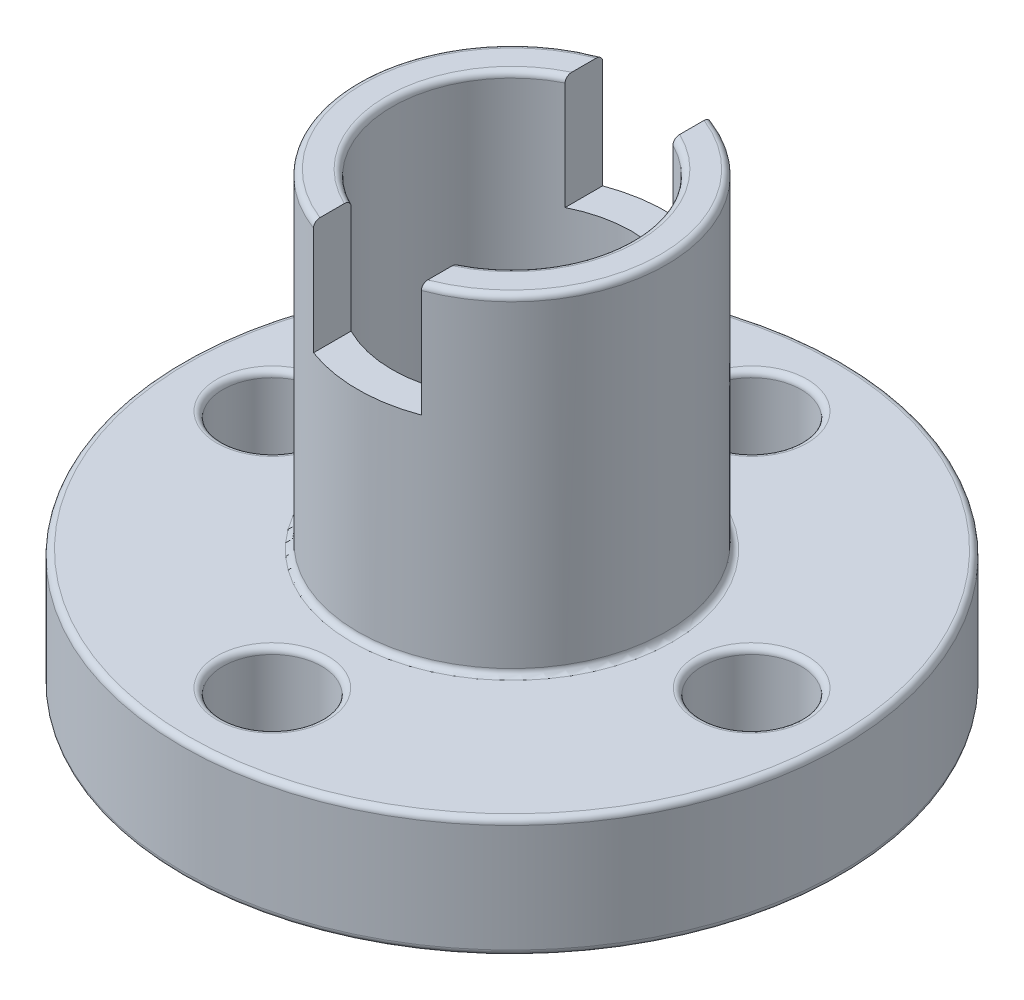
SolidWorks part; units mm, degrees
ref_plane "前视基准面" through (0, 0, 0) normal (0, 0, 1) x (1, 0, 0)
ref_plane "上视基准面" through (0, 0, 0) normal (0, 1, 0) x (1, 0, 0)
ref_plane "右视基准面" through (0, 0, 0) normal (1, 0, 0) x (0, 0, -1)
sketch "草图1" plane through (0, 0, 0) normal (0, 1, 0) x (1, 0, 0)
  circle A0 centre (0, 0) radius 4
  circle A1 centre (0, 0) radius 5.15
  circle A2 centre (0, 0) radius 11
  circle A3 centre (0, 0) radius 8 construction
  circle A4 centre (0, 8) radius 1.65
  circle A5 centre (8, 0) radius 1.65
  circle A6 centre (0, -8) radius 1.65
  circle A7 centre (-8, 0) radius 1.65
  dimension "D1" = 22
  dimension "D2" = 10.3
  dimension "D3" = 8
  dimension "D4" = 16
  dimension "D5" = 3.3
  dimension "D6" = 4
extrude "凸台-拉伸1" add sketch "草图1" along normal blind 4 contours A2 A7 A6 A5 A4 A1 region at (-10.6889, 0, 0)
extrude "凸台-拉伸2" add sketch "草图1<3>" along normal blind 15 contours A1 A0 region at (-5.0043, 0, 0)
sketch "草图1<3>" plane through (0, 0, 0) normal (0, 1, 0) x (1, 0, 0) same geometry as "草图1"
fillet "圆角1" radius 0.2 14 edges at (0, 15, 5.15) (0, 15, 4) (0, 4, 11) (0, 4, 5.15) (0, 4, -6.35) (8, 4, 1.65) (0, 4, 9.65) (-8, 4, 1.65) (0, 0, 4) (0, 0, 11) (0, 0, -6.35) (8, 0, 1.65) (0, 0, 9.65) (-8, 0, 1.65)
sketch "草图2" plane through (0, 0, 0) normal (0, 0, 1) x (1, 0, 0)
  line L0 (0, 17.5637) -> (0, -3.2504)
  line L1 (-4.95, 15) -> (4.95, 15)
  line L2 (4.95, 15) -> (-4.95, 15) construction
  line L3 (-4.95, 11.2) -> (4.95, 11.2)
  line L4 (-1.8, 17.5637) -> (-1.8, -3.2504)
  line L5 (1.8, 17.5637) -> (1.8, -3.2504)
  arc A1 (-4.95, 15) -> (-5.15, 14.8) centre (-4.95, 14.8) ccw construction
  dimension "D1" = 3.8
  dimension "D2" = 1.8
  dimension "D3" = 1.8
extrude "切除-拉伸1" cut sketch "草图2" against normal through all both and the other way through all contours L1 L4 L3 L0 | L5 L1 L0 L3 region at (0.9, 13.1, 0) region at (-0.9, 13.1, 0)
